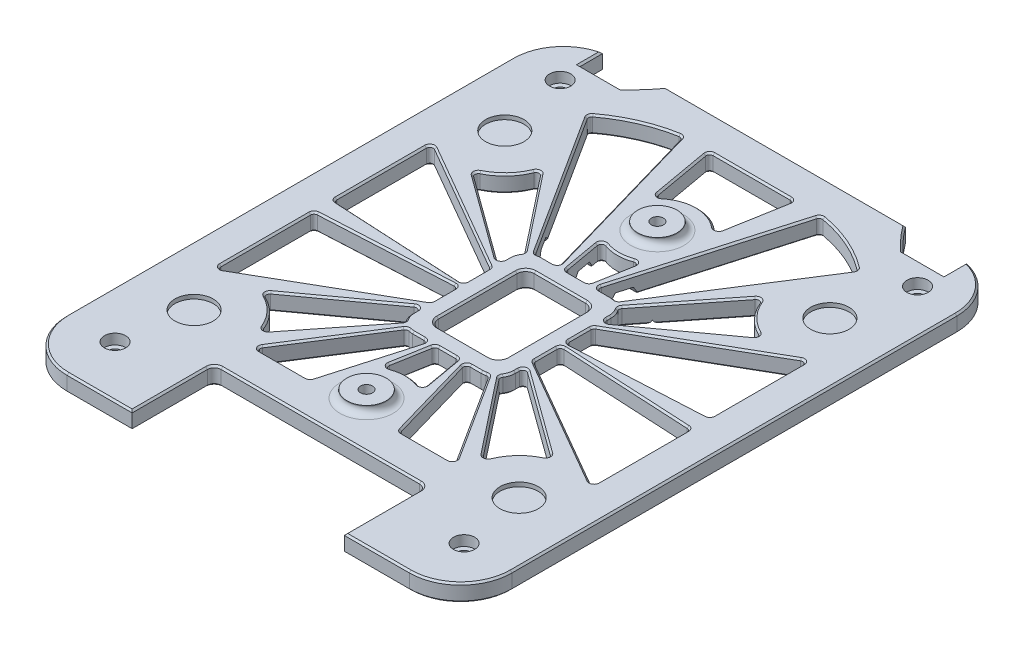
SolidWorks part; units mm, degrees
ref_plane "Front Plane" through (0, 0, 0) normal (0, 0, 1) x (1, 0, 0)
ref_plane "Top Plane" through (0, 0, 0) normal (0, 1, 0) x (1, 0, 0)
ref_plane "Right Plane" through (0, 0, 0) normal (1, 0, 0) x (0, 0, -1)
sketch "Sketch1" plane through (0, 0, 0) normal (0, 1, 0) x (1, 0, 0)
  line L0 (65, 160) -> (65, 24) construction
  line L5 (96, 0) -> (96, 22)
  line L7 (11.8, 153.04) -> (23.8, 153.04)
  line L9 (11.8, 153.04) -> (11.8, 159.6547)
  line L10 (118.2, 153.04) -> (106.2, 153.04)
  line L11 (118.2, 153.04) -> (118.2, 159.6547)
  line L18 (18, 160) -> (18, 155.5)
  line L19 (16.5, 154) -> (12.5, 154)
  line L20 (11, 155.5) -> (11, 159.4568)
  line L21 (0, 145) -> (0, 15)
  line L22 (15, 0) -> (34, 0)
  line L23 (34, 0) -> (34, 22.5)
  line L24 (35.5, 24) -> (90.5, 24)
  line L25 (96, 18.5) -> (96, 0)
  line L26 (96, 0) -> (115, 0)
  line L27 (130, 15) -> (130, 145)
  line L28 (119, 159.4568) -> (119, 155.5)
  line L29 (117.5, 154) -> (113.5, 154)
  line L30 (112, 155.5) -> (112, 160)
  line L31 (112, 160) -> (18, 160)
  line L35 (0, 145) -> (0, 15)
  line L36 (15, 0) -> (34, 0)
  line L37 (34, 0) -> (34, 22)
  line L38 (36, 24) -> (94, 24)
  line L40 (96, 0) -> (115, 0)
  line L41 (130, 15) -> (130, 145)
  line L45 (100, 160) -> (30, 160)
  circle A6 centre (116, 15) radius 1.75
  circle A7 centre (14, 15) radius 1.75
  circle A8 centre (65, 37.5) radius 1.75
  arc A10 (16.5, 154) -> (18, 155.5) centre (16.5, 155.5) ccw
  arc A11 (11, 155.5) -> (12.5, 154) centre (12.5, 155.5) ccw
  arc A12 (11, 159.4568) -> (0, 145) centre (15, 145) ccw
  arc A13 (0, 15) -> (15, 0) centre (15, 15) ccw
  arc A14 (35.5, 24) -> (34, 22.5) centre (35.5, 22.5) ccw
  arc A15 (96, 18.5) -> (90.5, 24) centre (90.5, 18.5) ccw
  arc A16 (115, 0) -> (130, 15) centre (115, 15) ccw
  arc A17 (130, 145) -> (119, 159.4568) centre (115, 145) ccw
  arc A18 (117.5, 154) -> (119, 155.5) centre (117.5, 155.5) ccw
  arc A19 (112, 155.5) -> (113.5, 154) centre (113.5, 155.5) ccw
  arc A22 (11, 159.4568) -> (0, 145) centre (15, 145) ccw
  arc A23 (0, 15) -> (15, 0) centre (15, 15) ccw
  arc A26 (115, 0) -> (130, 15) centre (115, 15) ccw
  arc A27 (130, 145) -> (119, 159.4568) centre (115, 145) ccw
  circle A30 centre (65, 122.5) radius 1.75
  circle A31 centre (12.78, 146.3) radius 1.75
  circle A32 centre (117.22, 146.3) radius 1.75
  arc A33 (36, 24) -> (34, 22) centre (36, 22) ccw
  arc A34 (94, 24) -> (96, 22) centre (94, 22) cw
  arc A35 (11, 159.4568) -> (11.8, 159.6547) centre (15, 145) cw
  arc A36 (23.8, 153.04) -> (30, 160) centre (-10.2724, 189.6333) ccw
  arc A37 (106.2, 153.04) -> (100, 160) centre (140.2724, 189.6333) cw
  arc A38 (119, 159.4568) -> (118.2, 159.6547) centre (115, 145) ccw
  dimension "D4" = 3.5
  dimension "D5" = 4
  dimension "D8" = 50
  dimension "D11" = 37.5
  dimension "D12" = 37.5
  dimension "D13" = 3.5
  dimension "D14" = 3.5
  dimension "D19" = 3.5
  dimension "D20" = 3.5
  dimension "D21" = 3.5
  dimension "D2" = 13.7
  dimension "D3" = 12.78
  dimension "D6" = 11.8
  dimension "D7" = 6.74
  dimension "D9" = 12
  dimension "D10" = 35
  dimension "D15" = 15
  dimension "D16" = 15
  dimension "D17" = 102
  dimension "D18" = 51
  dimension "D1" = 0
extrude "Boss-Extrude1" add sketch "Sketch1" along normal blind 5
chamfer "Chamfer1" distance 1.55 angle 45 2 edges at (65, 0, -35.75) (65, 0, -120.75)
sketch "Sketch2" plane through (0, 5, 0) normal (0, 1, 0) x (1, 0, 0)
  line L26 (15, 145) -> (15, 15)
  line L27 (15, 138.04) -> (15, 39) construction
  line L29 (100, 145) -> (36.9808, 145)
  line L30 (93.0192, 145) -> (36.9808, 145) construction
  line L40 (29.264, 138.04) -> (11.8, 138.04)
  line L41 (118.2, 138.04) -> (100.736, 138.04)
  line L42 (115, 138.04) -> (100.736, 138.04) construction
  line L43 (29.264, 138.04) -> (15, 138.04) construction
  line L45 (115, 15) -> (115, 145)
  line L46 (115, 39) -> (115, 138.04) construction
  line L48 (94, 39) -> (36, 39)
  line L49 (115, 39) -> (15, 39) construction
  circle A2 centre (65, 122.5) radius 11.75
  circle A3 centre (65, 122.5) radius 11.75 construction
  circle A5 centre (65, 37.5) radius 11.75
  circle A6 centre (65, 37.5) radius 11.75 construction
  arc A22 (34.0217, 142.062) -> (36.9808, 145) centre (-10.2724, 189.6333) ccw
  arc A28 (87.9183, 151.11) -> (100.736, 138.04) centre (140.2724, 189.6333) ccw
  arc A29 (93.0192, 145) -> (100.736, 138.04) centre (140.2724, 189.6333) ccw construction
  arc A30 (29.264, 138.04) -> (42.0817, 151.11) centre (-10.2724, 189.6333) ccw
  arc A31 (29.264, 138.04) -> (36.9808, 145) centre (-10.2724, 189.6333) ccw construction
  arc A33 (93.0192, 145) -> (76.6539, 39) centre (166.3728, 79.4116) ccw
  arc A34 (36.9808, 145) -> (53.3461, 39) centre (-36.3728, 79.4116) cw
  arc A35 (111, 22) -> (94, 39) centre (94, 22) ccw
  arc A36 (36, 39) -> (19, 22) centre (36, 22) ccw
  arc A41 (36.9808, 145) -> (53.3461, 39) centre (78.1854, 97.0983) ccw
  arc A42 (93.0192, 145) -> (76.6539, 39) centre (51.8146, 97.0983) cw
  dimension "D1" = 10
  dimension "D2" = 10
  dimension "D3" = 15
  dimension "D4" = 15
  dimension "D5" = 15
  dimension "D6" = 15
  dimension "D7" = 15
  dimension "D8" = 15
extrude "Cut-Extrude1" [suppressed] cut sketch "Sketch2" against normal up to next
sketch "Sketch5" plane through (0, 5, 0) normal (0, 1, 0) x (1, 0, 0)
  line L0 (65, 24) -> (65, 160) construction
  line L1 (36, 24) -> (94, 24) construction
  line L2 (100, 160) -> (30, 160) construction
  line L3 (0, 80) -> (130, 80) construction
  line L4 (0, 145) -> (0, 15) construction
  line L5 (130, 15) -> (130, 145) construction
  circle A0 centre (17.5, 34.6) radius 5.6
  circle A1 centre (65, 37.5) radius 1.75 construction
  circle A2 centre (65, 122.5) radius 1.75 construction
  circle A3 centre (17.5, 125.4) radius 5.6
  circle A4 centre (112.5, 34.6) radius 5.6
  circle A5 centre (112.5, 125.4) radius 5.6
  dimension "D1" = 11.2
  dimension "D3" = 2.9
  dimension "D4" = 42.5
  dimension "D2" = 47.5
extrude "Cut-Extrude3" cut sketch "Sketch5" against normal blind 1.2
sketch "Sketch6" plane through (0, 5, 0) normal (0, 1, 0) x (1, 0, 0)
  line L0 (130, 15) -> (130, 145) construction
  line L1 (0, 80) -> (130, 80) construction
  line L2 (0, 145) -> (0, 15) construction
  line L3 (50, 99) -> (50, 61) construction
  line L4 (50, 61) -> (80, 61) construction
  line L5 (80, 99) -> (80, 61) construction
  line L6 (50, 99) -> (80, 99) construction
  line L7 (65, 80) -> (105.255, 143.04) construction
  line L8 (65, 80) -> (97.4892, 121.153) construction
  line L9 (65, 80) -> (120, 111.7212) construction
  line L10 (65, 80) -> (107.2894, 110.6959) construction
  line L11 (65, 80) -> (85.1379, 150) construction
  line L12 (65, 80) -> (77.4055, 150) construction
  line L13 (65, 80) -> (120, 82.8824) construction
  line L14 (61.6328, 99) -> (68.3672, 99)
  line L15 (68.3672, 99) -> (70.7122, 112.2319)
  line L16 (77.4055, 150) -> (73.8929, 130.1798)
  line L17 (77.4055, 150) -> (52.5945, 150)
  line L23 (70.466, 99) -> (85.1379, 150)
  line L24 (65, 160) -> (65, 24) construction
  line L29 (100, 160) -> (30, 160) construction
  line L30 (36, 24) -> (94, 24) construction
  line L32 (55, 94) -> (75, 94) construction
  line L33 (55, 94) -> (55, 66) construction
  line L34 (55, 66) -> (75, 66) construction
  line L35 (75, 94) -> (75, 66) construction
  line L36 (10, 143.04) -> (10, 15)
  line L37 (15, 10) -> (24, 10)
  line L38 (24, 10) -> (24, 22)
  line L39 (36, 34) -> (94, 34)
  line L40 (106, 22) -> (106, 10)
  line L41 (106, 10) -> (115, 10)
  line L42 (120, 15) -> (120, 143.04)
  line L43 (120, 143.04) -> (102.4695, 143.04)
  line L44 (95.2258, 150) -> (34.7742, 150)
  line L45 (27.5305, 143.04) -> (10, 143.04)
  line L46 (10, 143.04) -> (10, 15) construction
  line L47 (15, 10) -> (24, 10) construction
  line L48 (24, 10) -> (24, 22) construction
  line L49 (36, 34) -> (94, 34) construction
  line L50 (106, 22) -> (106, 10) construction
  line L51 (106, 10) -> (115, 10) construction
  line L52 (120, 15) -> (120, 143.04) construction
  line L53 (120, 143.04) -> (102.4695, 143.04) construction
  line L54 (95.2258, 150) -> (34.7742, 150) construction
  line L55 (27.5305, 143.04) -> (10, 143.04) construction
  line L57 (80, 90.8878) -> (107.2894, 110.6959)
  line L58 (120, 111.7212) -> (120, 82.8824)
  line L59 (120, 82.8824) -> (80, 80.7861)
  line L60 (80, 80.7861) -> (80, 88.6512)
  line L61 (80, 88.6512) -> (120, 111.7212)
  line L64 (57.5, 94) -> (72.5, 94)
  line L65 (75, 68.5) -> (75, 91.5)
  line L66 (80, 90.8878) -> (80, 94)
  line L67 (97.4892, 121.153) -> (78.7041, 97.3585)
  line L68 (104.3576, 141.6346) -> (76.8946, 98.6271)
  line L69 (70.466, 99) -> (75, 99)
  line L70 (57.5, 66) -> (72.5, 66)
  line L71 (80, 79.2139) -> (80, 71.3488)
  line L72 (120, 77.1176) -> (80, 79.2139)
  line L73 (120, 48.2788) -> (120, 77.1176)
  line L74 (80, 71.3488) -> (120, 48.2788)
  line L75 (97.4892, 38.847) -> (78.7041, 62.6415)
  line L76 (80, 69.1122) -> (107.2894, 49.3041)
  line L77 (80, 69.1122) -> (80, 66)
  line L78 (70.466, 61) -> (85.1379, 10) construction
  line L79 (70.466, 61) -> (75, 61)
  line L80 (104.3576, 18.3654) -> (76.8946, 61.3729) construction
  line L81 (68.3672, 61) -> (70.7122, 47.7681)
  line L82 (61.6328, 61) -> (68.3672, 61)
  line L87 (78.2335, 34) -> (94, 34)
  line L88 (94, 34) -> (94.3739, 34)
  line L89 (70.466, 61) -> (78.2335, 34)
  line L90 (76.8946, 61.3729) -> (94.3739, 34)
  line L91 (61.6328, 61) -> (59.2878, 47.7681)
  line L92 (59.534, 61) -> (55, 61)
  line L93 (59.534, 61) -> (51.7665, 34)
  line L94 (51.7665, 34) -> (36, 34)
  line L95 (36, 34) -> (35.6261, 34)
  line L96 (53.1054, 61.3729) -> (35.6261, 34)
  line L97 (50, 69.1122) -> (22.7106, 49.3041)
  line L98 (50, 69.1122) -> (50, 66)
  line L99 (32.5108, 38.847) -> (51.2959, 62.6415)
  line L100 (10, 77.1176) -> (50, 79.2139)
  line L101 (10, 48.2788) -> (10, 77.1176)
  line L102 (50, 71.3488) -> (10, 48.2788)
  line L103 (50, 79.2139) -> (50, 71.3488)
  line L104 (50, 80.7861) -> (50, 88.6512)
  line L105 (10, 82.8824) -> (50, 80.7861)
  line L106 (10, 111.7212) -> (10, 82.8824)
  line L107 (50, 88.6512) -> (10, 111.7212)
  line L108 (32.5108, 121.153) -> (51.2959, 97.3585)
  line L109 (50, 90.8878) -> (22.7106, 110.6959)
  line L110 (50, 90.8878) -> (50, 94)
  line L111 (59.534, 99) -> (44.8621, 150)
  line L112 (59.534, 99) -> (55, 99)
  line L113 (25.6424, 141.6346) -> (53.1054, 98.6271)
  line L114 (61.6328, 99) -> (59.2878, 112.2319)
  line L115 (52.5945, 150) -> (56.1071, 130.1798)
  line L116 (55, 68.5) -> (55, 91.5)
  arc A0 (55, 61) -> (53.1054, 61.3729) centre (55, 66) cw
  arc A1 (97.4892, 121.153) -> (107.2894, 110.6959) centre (112.5, 125.4) ccw
  arc A2 (59.2878, 112.2319) -> (70.7122, 112.2319) centre (65, 122.5) ccw
  arc A3 (73.8929, 130.1798) -> (56.1071, 130.1798) centre (65, 122.5) ccw
  circle A4 centre (72.5, 91.5) radius 2.5 construction
  arc A5 (72.5, 94) -> (75, 91.5) centre (72.5, 91.5) cw
  circle A6 centre (75, 94) radius 5 construction
  arc A7 (78.7041, 97.3585) -> (80, 94) centre (75, 94) cw
  arc A8 (75, 99) -> (76.8946, 98.6271) centre (75, 94) cw
  arc A9 (85.1379, 150) -> (120, 111.7212) centre (78.8262, 109.2371) cw construction
  arc A10 (85.1379, 150) -> (104.3576, 141.6346) centre (78.8262, 109.2371) cw
  arc A11 (72.5, 66) -> (75, 68.5) centre (72.5, 68.5) ccw
  arc A12 (97.4892, 38.847) -> (107.2894, 49.3041) centre (112.5, 34.6) cw
  arc A13 (78.7041, 62.6415) -> (80, 66) centre (75, 66) ccw
  arc A14 (75, 61) -> (76.8946, 61.3729) centre (75, 66) ccw
  arc A15 (85.1379, 10) -> (104.3576, 18.3654) centre (78.8262, 50.7629) ccw construction
  arc A16 (59.2878, 47.7681) -> (70.7122, 47.7681) centre (65, 37.5) cw
  arc A18 (32.5108, 38.847) -> (22.7106, 49.3041) centre (17.5, 34.6) ccw
  arc A19 (51.2959, 62.6415) -> (50, 66) centre (55, 66) cw
  arc A20 (32.5108, 121.153) -> (22.7106, 110.6959) centre (17.5, 125.4) cw
  arc A21 (51.2959, 97.3585) -> (50, 94) centre (55, 94) ccw
  arc A22 (55, 99) -> (53.1054, 98.6271) centre (55, 94) ccw
  arc A23 (44.8621, 150) -> (25.6424, 141.6346) centre (51.1738, 109.2371) ccw
  arc A24 (57.5, 66) -> (55, 68.5) centre (57.5, 68.5) cw
  arc A25 (57.5, 94) -> (55, 91.5) centre (57.5, 91.5) ccw
  circle A30 centre (17.5, 125.4) radius 15.6
  circle A31 centre (17.5, 125.4) radius 15.6 construction
  circle A33 centre (17.5, 34.6) radius 15.6
  circle A34 centre (17.5, 34.6) radius 15.6 construction
  circle A36 centre (112.5, 125.4) radius 15.6
  circle A37 centre (112.5, 125.4) radius 15.6 construction
  circle A39 centre (112.5, 34.6) radius 15.6
  circle A40 centre (112.5, 34.6) radius 15.6 construction
  circle A50 centre (65, 122.5) radius 11.75
  circle A51 centre (65, 122.5) radius 11.75 construction
  circle A53 centre (65, 37.5) radius 11.75
  circle A54 centre (65, 37.5) radius 11.75 construction
  arc A56 (10, 15) -> (15, 10) centre (15, 15) ccw
  arc A57 (36, 34) -> (24, 22) centre (36, 22) ccw
  arc A58 (106, 22) -> (94, 34) centre (94, 22) ccw
  arc A59 (115, 10) -> (120, 15) centre (115, 15) ccw
  arc A60 (95.2258, 150) -> (102.4695, 143.04) centre (140.2724, 189.6333) ccw
  arc A61 (27.5305, 143.04) -> (34.7742, 150) centre (-10.2724, 189.6333) ccw
  arc A62 (10, 15) -> (15, 10) centre (15, 15) ccw construction
  arc A63 (36, 34) -> (24, 22) centre (36, 22) ccw construction
  arc A64 (106, 22) -> (94, 34) centre (94, 22) ccw construction
  arc A65 (115, 10) -> (120, 15) centre (115, 15) ccw construction
  arc A66 (95.2258, 150) -> (102.4695, 143.04) centre (140.2724, 189.6333) ccw construction
  arc A67 (27.5305, 143.04) -> (34.7742, 150) centre (-10.2724, 189.6333) ccw construction
  point P26 (65, 94)
  point P38 (75, 80)
  point P104 (75, 80)
  point P163 (65, 66)
  point P168 (65, 94)
  dimension "D14" = 5
  dimension "D16" = 10
  dimension "D17" = 41.2487
  dimension "D8" = 55
  dimension "D10" = 14
  dimension "D12" = 3
  dimension "D13" = 6
  dimension "D15" = 6
  dimension "D1" = 10
  dimension "D2" = 10
  dimension "D3" = 10
  dimension "D4" = 10
  dimension "D5" = 10
  dimension "D6" = 10
  dimension "D7" = 10
extrude "Cut-Extrude4" cut sketch "Sketch6" against normal up to next
sketch "Sketch7" plane through (0, 5, 0) normal (0, 1, 0) x (1, 0, 0)
  circle A0 centre (65, 37.5) radius 5.75
  circle A1 centre (65, 122.5) radius 5.75
  circle A2 centre (65, 122.5) radius 1.75 construction
  circle A3 centre (65, 37.5) radius 1.75 construction
  circle A4 centre (65, 122.5) radius 1.75
  circle A5 centre (65, 37.5) radius 1.75
  dimension "D1" = 11.5
  dimension "D2" = 11.5
extrude "Boss-Extrude2" add sketch "Sketch7" along normal blind 2.2
fillet "Fillet1" radius 2 2 edges at (65, 5, -128.25) (65, 5, -43.25)
sketch "Sketch8" plane through (0, 5, 0) normal (0, 1, 0) x (1, 0, 0)
  circle A0 centre (12.78, 146.3) radius 3.1
  circle A1 centre (14, 15) radius 3.1
  circle A2 centre (117.22, 146.3) radius 3.1
  circle A3 centre (116, 15) radius 3.1
  dimension "D1" = 6.2
  dimension "D2" = 6.2
  dimension "D3" = 6.2
  dimension "D4" = 6.2
extrude "Cut-Extrude5" cut sketch "Sketch8" against normal blind 3
sketch "Sketch3" plane through (0, 0, 0) normal (0, -1, 0) x (1, 0, 0)
  text T0 "<b>gen3.0.0</b>" font "Century Gothic" height 4.5
extrude "Cut-Extrude2" cut sketch "Sketch3" against normal blind 0.5
fillet "Fillet2" radius 1 60 edges at (56.1071, 2.5, -130.1798) (73.8929, 2.5, -130.1798) (104.3576, 2.5, -141.6346) (76.8946, 2.5, -98.6271) (78.7041, 2.5, -97.3585) (107.2894, 2.5, -110.6959) (80, 2.5, -80.7861) (120, 2.5, -82.8824) (120, 2.5, -48.2788) (80, 2.5, -69.1122) (78.7041, 2.5, -62.6415) (107.2894, 2.5, -49.3041) (94.3739, 2.5, -34) (70.7122, 2.5, -47.7681) (59.2878, 2.5, -47.7681) (35.6261, 2.5, -34) (22.7106, 2.5, -49.3041) (97.4892, 2.5, -38.847) (78.2335, 2.5, -34) (51.7665, 2.5, -34) (32.5108, 2.5, -38.847) (51.2959, 2.5, -62.6415) (10, 2.5, -48.2788) (50, 2.5, -90.8878) (51.2959, 2.5, -97.3585) (32.5108, 2.5, -121.153) (80, 2.5, -71.3488) (80, 2.5, -90.8878) (53.1054, 2.5, -98.6271) (61.6328, 2.5, -99) (70.466, 2.5, -99) (68.3672, 2.5, -99) (59.534, 2.5, -99) (50, 2.5, -71.3488) (50, 2.5, -80.7861) (10, 2.5, -82.8824) (22.7106, 2.5, -110.6959) (53.1054, 2.5, -61.3729) (61.6328, 2.5, -61) (70.466, 2.5, -61) (80, 2.5, -79.2139) (80, 2.5, -88.6512) (10, 2.5, -77.1176) (10, 2.5, -111.7212) (25.6424, 2.5, -141.6346) (59.2878, 2.5, -112.2319) (85.1379, 2.5, -150) (52.5945, 2.5, -150) (120, 2.5, -77.1176) (76.8946, 2.5, -61.3729) (68.3672, 2.5, -61) (59.534, 2.5, -61) (50, 2.5, -69.1122) (50, 2.5, -88.6512) (50, 2.5, -79.2139) (97.4892, 2.5, -121.153) (120, 2.5, -111.7212) (70.7122, 2.5, -112.2319) (77.4055, 2.5, -150) (44.8621, 2.5, -150)
sketch "Sketch9" plane through (0, 0, 0) normal (0, -1, 0) x (1, 0, 0)
  line L0 (100, -160) -> (30, -160) construction
  line L1 (82.5, -107.5) -> (47.5, -107.5)
  line L2 (82.5, -107.5) -> (82.5, -103.5)
  line L3 (82.5, -103.5) -> (47.5, -103.5)
  line L4 (47.5, -107.5) -> (47.5, -103.5)
  line L5 (130, -15) -> (130, -145) construction
  dimension "D1" = 4
  dimension "D2" = 35
  dimension "D3" = 52.5
  dimension "D4" = 47.5
extrude "Cut-Extrude6" cut sketch "Sketch9" against normal blind 2
chamfer "Chamfer2" distance 1.2 angle 60 8 edges at (48.7469, 0, -103.5) (47.5, 0, -105.4527) (81.2531, 0, -103.5) (82.5, 0, -105.4527) (70.4626, 0, -103.5) (59.5374, 0, -103.5) (58.6076, 0, -107.5) (71.3924, 0, -107.5) first distance on face at (65, 0, -111.8146)
chamfer "Chamfer3" distance 0.5 angle 45 40 edges at (0, 5, -80) (4.3934, 5, -4.3934) (24.5, 5, 0) (34, 5, -11) (34.5858, 5, -23.4142) (65, 5, -24) (95.4142, 5, -23.4142) (96, 5, -11) (105.5, 5, 0) (125.6066, 5, -4.3934) (130, 5, -80) (126.6833, 5, -154.4074) (118.2, 5, -156.3473) (112.2, 5, -153.04) (102.9375, 5, -156.3752) (65, 5, -160) (27.0625, 5, -156.3752) (17.8, 5, -153.04) (11.8, 5, -156.3473) (3.3167, 5, -154.4074) (118.2, 0, -156.3473) (112.2, 0, -153.04) (102.9375, 0, -156.3752) (126.6833, 0, -154.4074) (130, 0, -80) (125.6066, 0, -4.3934) (105.5, 0, 0) (96, 0, -11) (95.4142, 0, -23.4142) (65, 0, -24) (34.5858, 0, -23.4142) (34, 0, -11) (24.5, 0, 0) (4.3934, 0, -4.3934) (0, 0, -80) (3.3167, 0, -154.4074) (11.8, 0, -156.3473) (17.8, 0, -153.04) (27.0625, 0, -156.3752) (65, 0, -160)
chamfer "Chamfer4" distance 0.5 angle 45 284 edges at (75, 5, -80) (74.2678, 5, -93.2678) (74.2678, 5, -66.7322) (65, 5, -94) (65, 5, -66) (55.7322, 5, -93.2678) (55.7322, 5, -66.7322) (55, 5, -80) (69.4467, 5, -54.9087) (68.1713, 5, -60.7663) (70.0373, 5, -48.7018) (65, 5, -61) (65, 5, -49.25) (61.8287, 5, -60.7663) (59.9627, 5, -48.7018) (60.5533, 5, -54.9087) (59.0047, 5, -60.6015) (55.5707, 5, -47.2235) (56.6029, 5, -61) (51.6151, 5, -34.2011) (54.3835, 5, -61.0382) (44.2324, 5, -34) (53.163, 5, -61.112) (36.5742, 5, -34.5195) (44.6486, 5, -48.1294) (51.0245, 5, -62.6082) (42.2264, 5, -51.1534) (50.2183, 5, -64.5386) (32.7188, 5, -39.9102) (50, 5, -66.5753) (28.8664, 5, -45.2847) (49.4542, 5, -68.0416) (23.741, 5, -49.4511) (36.2811, 5, -59.1543) (30.4996, 5, -60.1019) (49.8659, 5, -71.4262) (10.4998, 5, -49.1441) (50, 5, -75.0433) (10, 5, -63.0893) (49.6884, 5, -78.8855) (10.2746, 5, -76.857) (29.9477, 5, -78.163) (29.9477, 5, -81.837) (49.6884, 5, -81.1145) (10.2746, 5, -83.143) (50, 5, -84.9567) (10, 5, -96.9107) (49.8659, 5, -88.5738) (10.4998, 5, -110.8559) (30.4996, 5, -99.8981) (49.4542, 5, -91.9584) (36.2811, 5, -100.8457) (50, 5, -93.4247) (23.741, 5, -110.5489) (50.2183, 5, -95.4614) (28.8664, 5, -114.7153) (51.0245, 5, -97.3918) (32.7188, 5, -120.0898) (42.2264, 5, -108.8466) (53.163, 5, -98.888) (39.4121, 5, -120.0711) (54.3835, 5, -98.9618) (25.994, 5, -141.5789) (56.6029, 5, -99) (34.7237, 5, -147.0636) (59.0047, 5, -99.3985) (44.6765, 5, -149.7162) (52.1376, 5, -124.7103) (54.2888, 5, -140.4401) (56.42, 5, -131.2885) (53.021, 5, -149.6425) (65, 5, -134.25) (65, 5, -150) (73.58, 5, -131.2885) (76.979, 5, -149.6425) (75.7112, 5, -140.4401) (60.5533, 5, -105.0913) (61.8287, 5, -99.2337) (59.9627, 5, -111.2982) (65, 5, -99) (65, 5, -110.75) (68.1713, 5, -99.2337) (70.0373, 5, -111.2982) (69.4467, 5, -105.0913) (70.9953, 5, -99.3985) (77.8624, 5, -124.7103) (73.3971, 5, -99) (85.3235, 5, -149.7162) (75.6165, 5, -98.9618) (95.2763, 5, -147.0636) (76.837, 5, -98.888) (104.006, 5, -141.5789) (90.5879, 5, -120.0711) (78.9755, 5, -97.3918) (87.7736, 5, -108.8466) (79.7817, 5, -95.4614) (97.2812, 5, -120.0898) (80, 5, -93.4247) (101.1336, 5, -114.7153) (80.5458, 5, -91.9584) (106.259, 5, -110.5489) (93.7189, 5, -100.8457) (99.5004, 5, -99.8981) (80.1341, 5, -88.5738) (119.5002, 5, -110.8559) (80, 5, -84.9567) (120, 5, -96.9107) (80.3116, 5, -81.1145) (119.7254, 5, -83.143) (100.0523, 5, -81.837) (100.0523, 5, -78.163) (80.3116, 5, -78.8855) (119.7254, 5, -76.857) (80, 5, -75.0433) (120, 5, -63.0893) (80.1341, 5, -71.4262) (119.5002, 5, -49.1441) (99.5004, 5, -60.1019) (80.5458, 5, -68.0416) (93.7189, 5, -59.1543) (80, 5, -66.5753) (106.259, 5, -49.4511) (79.7817, 5, -64.5386) (101.1336, 5, -45.2847) (78.9755, 5, -62.6082) (97.2812, 5, -39.9102) (87.7736, 5, -51.1534) (76.837, 5, -61.112) (85.3514, 5, -48.1294) (75.6165, 5, -61.0382) (93.4258, 5, -34.5195) (73.3971, 5, -61) (85.7676, 5, -34) (70.9953, 5, -60.6015) (78.3849, 5, -34.2011) (74.4293, 5, -47.2235) (75, 0, -80) (74.2678, 0, -93.2678) (74.2678, 0, -66.7322) (65, 0, -94) (65, 0, -66) (55.7322, 0, -93.2678) (55.7322, 0, -66.7322) (55, 0, -80) (12.78, 0, -144.55) (117.22, 0, -148.05) (116, 0, -13.25) (14, 0, -13.25) (60.5533, 0, -54.9087) (59.9627, 0, -48.7018) (61.8287, 0, -60.7663) (65, 0, -49.25) (65, 0, -61) (70.0373, 0, -48.7018) (68.1713, 0, -60.7663) (69.4467, 0, -54.9087) (74.4293, 0, -47.2235) (70.9953, 0, -60.6015) (78.3849, 0, -34.2011) (73.3971, 0, -61) (85.7676, 0, -34) (75.6165, 0, -61.0382) (93.4258, 0, -34.5195) (76.837, 0, -61.112) (85.3514, 0, -48.1294) (87.7736, 0, -51.1534) (78.9755, 0, -62.6082) (97.2812, 0, -39.9102) (79.7817, 0, -64.5386) (101.1336, 0, -45.2847) (80, 0, -66.5753) (106.259, 0, -49.4511) (80.5458, 0, -68.0416) (93.7189, 0, -59.1543) (99.5004, 0, -60.1019) (119.5002, 0, -49.1441) (80.1341, 0, -71.4262) (120, 0, -63.0893) (80, 0, -75.0433) (119.7254, 0, -76.857) (80.3116, 0, -78.8855) (100.0523, 0, -78.163) (100.0523, 0, -81.837) (119.7254, 0, -83.143) (80.3116, 0, -81.1145) (120, 0, -96.9107) (80, 0, -84.9567) (119.5002, 0, -110.8559) (80.1341, 0, -88.5738) (99.5004, 0, -99.8981) (93.7189, 0, -100.8457) (80.8976, 0, -100.137) (78.9755, 0, -97.3918) (79.7817, 0, -95.4614) (80, 0, -93.4247) (80.5458, 0, -91.9584) (106.259, 0, -110.5489) (101.1336, 0, -114.7153) (97.2812, 0, -120.0898) (90.0286, 0, -111.7029) (93.7824, 0, -125.0737) (78.2755, 0, -100.7897) (71.1243, 0, -101.2882) (76.837, 0, -98.888) (70.9953, 0, -99.3985) (75.6165, 0, -98.9618) (73.3971, 0, -99) (70.2331, 0, -109.5285) (59.7669, 0, -109.5285) (70.0373, 0, -111.2982) (59.9627, 0, -111.2982) (65, 0, -110.75) (61.2672, 0, -101.0627) (68.7328, 0, -101.0627) (61.8287, 0, -99.2337) (68.1713, 0, -99.2337) (65, 0, -99) (51.7245, 0, -100.7897) (53.163, 0, -98.888) (58.8757, 0, -101.2882) (54.3835, 0, -98.9618) (59.0047, 0, -99.3985) (56.6029, 0, -99) (104.006, 0, -141.5789) (95.2763, 0, -147.0636) (85.3235, 0, -149.7162) (79.0741, 0, -128.9221) (75.7112, 0, -140.4401) (76.979, 0, -149.6425) (73.58, 0, -131.2885) (65, 0, -150) (65, 0, -134.25) (53.021, 0, -149.6425) (56.42, 0, -131.2885) (54.2888, 0, -140.4401) (50.9259, 0, -128.9221) (44.6765, 0, -149.7162) (34.7237, 0, -147.0636) (25.994, 0, -141.5789) (36.2176, 0, -125.0737) (49.1024, 0, -100.137) (39.9714, 0, -111.7029) (51.0245, 0, -97.3918) (32.7188, 0, -120.0898) (50.2183, 0, -95.4614) (28.8664, 0, -114.7153) (50, 0, -93.4247) (23.741, 0, -110.5489) (49.4542, 0, -91.9584) (36.2811, 0, -100.8457) (30.4996, 0, -99.8981) (10.4998, 0, -110.8559) (49.8659, 0, -88.5738) (10, 0, -96.9107) (50, 0, -84.9567) (10.2746, 0, -83.143) (49.6884, 0, -81.1145) (29.9477, 0, -81.837) (29.9477, 0, -78.163) (10.2746, 0, -76.857) (49.6884, 0, -78.8855) (10, 0, -63.0893) (50, 0, -75.0433) (10.4998, 0, -49.1441) (49.8659, 0, -71.4262) (30.4996, 0, -60.1019) (36.2811, 0, -59.1543) (49.4542, 0, -68.0416) (23.741, 0, -49.4511) (50, 0, -66.5753) (28.8664, 0, -45.2847) (50.2183, 0, -64.5386) (32.7188, 0, -39.9102) (51.0245, 0, -62.6082) (42.2264, 0, -51.1534) (44.6486, 0, -48.1294) (53.163, 0, -61.112) (36.5742, 0, -34.5195) (54.3835, 0, -61.0382) (44.2324, 0, -34) (56.6029, 0, -61) (51.6151, 0, -34.2011) (59.0047, 0, -60.6015) (55.5707, 0, -47.2235)
